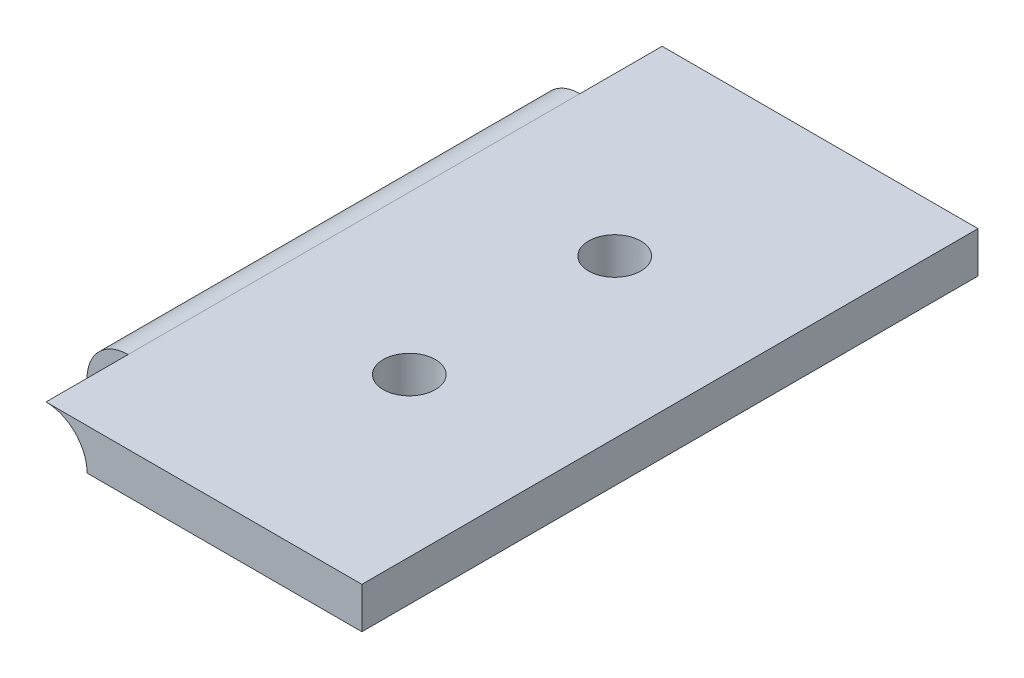
SolidWorks part; units mm, degrees
ref_plane "Front Plane" through (0, 0, 0) normal (0, 0, 1) x (1, 0, 0)
ref_plane "Top Plane" through (0, 0, 0) normal (0, 1, 0) x (1, 0, 0)
ref_plane "Right Plane" through (0, 0, 0) normal (1, 0, 0) x (0, 0, -1)
sketch "Sketch1" plane through (0, 0, 0) normal (0, 0, 1) x (1, 0, 0)
  line L0 (21.825, 0) -> (28.175, 0) construction
  line L1 (-73.5566, -122.4038) -> (0, 5) construction
  line L2 (0, 5) -> (250, 5) construction
  line L3 (21.825, 0) -> (28.175, 0)
  line L4 (-73.5566, -122.4038) -> (0, 5)
  line L5 (0, 5) -> (250, 5)
  line L6 (0, 0) -> (250, 0) construction
  line L7 (0, 0) -> (250, 0)
  line L8 (44.2265, 0) -> (5.7735, 0)
  line L9 (5.7735, 0) -> (5.7735, -5)
  line L10 (5.7735, -5) -> (44.2265, -5)
  line L11 (44.2265, -5) -> (44.2265, 0)
  line L12 (2.8868, 0) -> (-69.2265, -124.9038)
  line L13 (-73.5566, -122.4038) -> (-69.2265, -124.9038)
  line L14 (25, 0) -> (25, -5)
  circle A0 centre (5.7735, -5) radius 5
  circle A1 centre (5.7735, -5) radius 2.5
  point P13 (25, -5)
  point P14 (25, 0)
  point P19 (5.7735, 0)
  dimension "D4" = 10
  dimension "D5" = 5
  dimension "D1" = 120
  dimension "D2" = 5
  dimension "D3" = 5
extrude "Boss-Extrude1" add sketch "Sketch1" against normal blind 75 contours L10 L11 L8 L9
extrude "Boss-Extrude2" add sketch "Sketch1<4>" against normal blind 55 from offset 10 contours A1 L9 A0 L10 region at (5.6321, -1.25, 0) offset against normal yes
sketch "Sketch1<4>" plane through (0, 0, 0) normal (0, 0, 1) x (1, 0, 0) same geometry as "Sketch1"
sketch "Sketch5" plane through (0, -5, 0) normal (0, -1, 0) x (1, 0, 0)
  circle A0 centre (25, -25) radius 3.175 construction
  circle A1 centre (25, -50) radius 3.175 construction
  circle A2 centre (25, -25) radius 3.175
  circle A3 centre (25, -50) radius 3.175
extrude "Cut-Extrude8" cut sketch "Sketch5" against normal blind 55
extrude "Cut-Extrude9" cut sketch "Sketch1<14>" against normal blind 75 contours L10 A1 L9 region at (6.8345, -3.939, 0)
sketch "Sketch1<14>" plane through (0, 0, 0) normal (0, 0, 1) x (1, 0, 0) same geometry as "Sketch1"
extrude "Cut-Extrude10" cut sketch "Sketch1<15>" against normal blind 10 contours A1 L10 A0 L9 region at (8.2492, -2.5243, 0)
sketch "Sketch1<15>" plane through (0, 0, 0) normal (0, 0, 1) x (1, 0, 0) same geometry as "Sketch1"
extrude "Cut-Extrude11" cut sketch "Sketch1<16>" against normal blind 10 from offset 65 contours A1 L10 A0 L9 region at (8.2492, -2.5243, 0) offset against normal yes
sketch "Sketch1<16>" plane through (0, 0, 0) normal (0, 0, 1) x (1, 0, 0) same geometry as "Sketch1"
